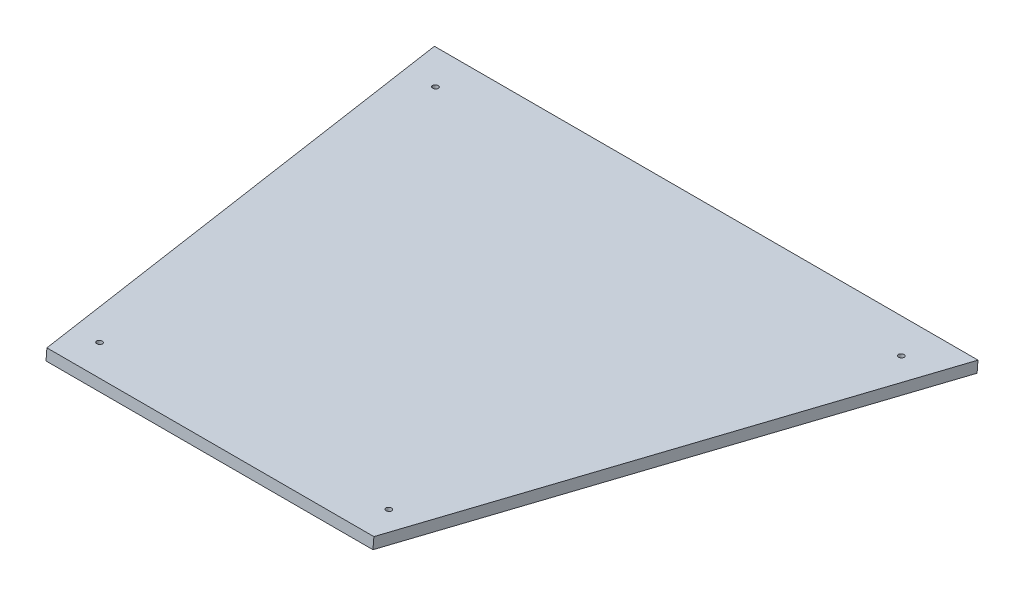
SolidWorks part; units mm, degrees
ref_plane "Front Plane" through (0, 0, 0) normal (0, 0, 1) x (1, 0, 0)
ref_plane "Top Plane" through (0, 0, 0) normal (0, 1, 0) x (1, 0, 0)
ref_plane "Right Plane" through (0, 0, 0) normal (1, 0, 0) x (0, 0, -1)
ref_plane "Plane1" through (-0.0008, -10571.5609, 872.0847) normal (0, -0.9966, 0.0822) x (-1, 0, 0)
sketch "Sketch1" plane through (-0.0008, -10571.5609, 872.0847) normal (0, -0.9966, 0.0822) x (-1, 0, 0)
  line L0 (927.9324, -1893.2884) -> (1306.8393, -1893.2884)
  line L1 (1306.8393, -1893.2884) -> (1432.3521, -1316.7398)
  line L2 (1432.3521, -1316.7398) -> (802.4196, -1316.7398)
  line L3 (802.4196, -1316.7398) -> (927.9324, -1893.2884)
  line L4 (802.4183, -1316.7398) -> (1432.3534, -1316.7398) construction
  line L5 (928.076, -1893.948) -> (801.0629, -1310.5075) construction
  line L6 (1433.7088, -1310.5075) -> (1306.6957, -1893.948) construction
  line L7 (1306.8419, -1893.2884) -> (927.9298, -1893.2884) construction
extrude "Boss-Extrude1" add sketch "Sketch1" along normal blind 12.7
sketch "Sketch2" plane through (-0.0008, -10571.5609, 872.0847) normal (0, 0.9966, -0.0822) x (1, 0, 0)
  line L0 (-927.9324, -1893.2884) -> (-1306.8393, -1893.2884) construction
  line L1 (-1306.8393, -1893.2884) -> (-1432.3521, -1316.7398) construction
  line L2 (-802.4196, -1316.7398) -> (-927.9324, -1893.2884) construction
  line L3 (-1432.3521, -1316.7398) -> (-802.4196, -1316.7398) construction
  circle A0 centre (-1284.9566, -1854.0196) radius 3.175
  circle A3 centre (-949.7975, -1853.9387) radius 3.175
  circle A4 centre (-1387.3011, -1360.7012) radius 3.175
  circle A6 centre (-847.4706, -1360.7012) radius 3.175
  dimension "D1" = 6.35
  dimension "D2" = 39.2688
  dimension "D3" = 29.735
  dimension "D4" = 6.35
  dimension "D5" = 39.3497
  dimension "D7" = 6.35
  dimension "D10" = 6.35
  dimension "D6" = 29.735
  dimension "D8" = 43.9614
  dimension "D9" = 34.6688
  dimension "D11" = 34.6688
  dimension "D12" = 43.9614
extrude "Cut-Extrude1" cut sketch "Sketch2" against normal through all
